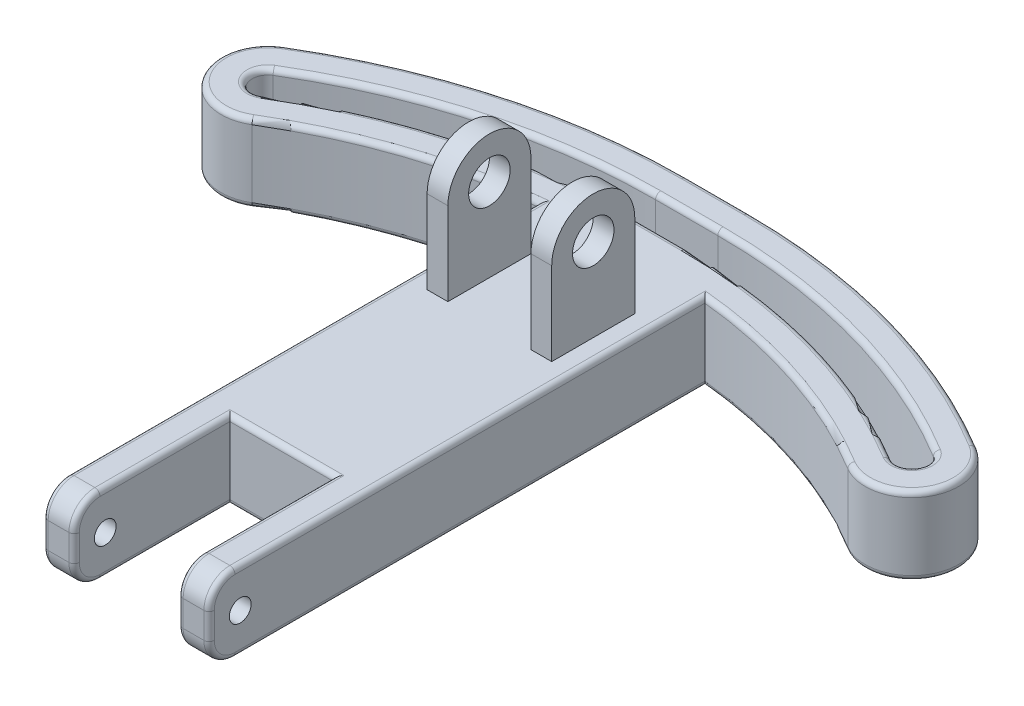
SolidWorks part; units mm, degrees
material "AISI 1020"
ref_plane "Front" through (0, 0, 0) normal (0, 0, 1) x (1, 0, 0)
ref_plane "Top" through (0, 0, 0) normal (0, 1, 0) x (1, 0, 0)
ref_plane "Right" through (0, 0, 0) normal (1, 0, 0) x (0, 0, -1)
sketch "Sketch1" plane through (0, 0, 0) normal (0, 1, 0) x (1, 0, 0)
  line L2 (70.9937, 406.4) -> (70.9937, 152.4)
  line L4 (70.9937, 482.6) -> (45.5937, 482.6)
  line L6 (20.1937, 406.4) -> (20.1937, 152.4)
  line L7 (70.9937, 457.2) -> (70.9937, 457.2)
  line L8 (70.9937, 406.4) -> (70.9937, 378.1596)
  line L9 (70.9937, 457.2) -> (70.9937, 378.1596) construction
  line L10 (70.9937, 457.2) -> (20.1937, 457.2)
  line L11 (70.9937, 431.8) -> (20.1937, 431.8)
  line L12 (20.1937, 482.6) -> (45.5937, 482.6)
  line L13 (57.6792, 127) -> (87.9271, 127)
  line L14 (87.9271, 127) -> (87.9271, 0)
  line L15 (87.9271, 0) -> (113.3271, 0)
  line L16 (113.3271, 0) -> (113.3271, 152.4)
  line L17 (113.3271, 152.4) -> (70.9937, 152.4)
  line L19 (20.1937, 152.4) -> (-22.1396, 152.4)
  line L20 (-22.1396, 152.4) -> (-22.1396, 0)
  line L21 (-22.1396, 0) -> (3.2604, 0)
  line L22 (3.2604, 0) -> (3.2604, 127)
  line L23 (3.2604, 127) -> (33.5083, 127)
  line L24 (90.9704, 127) -> (57.6792, 127)
  line L25 (86.1988, 127) -> (90.9704, 127)
  line L26 (33.5083, 127) -> (86.1988, 127)
  line L27 (45.5937, 482.6) -> (45.5937, 378.1596) construction
  arc A0 (70.9937, 406.4) -> (288.4438, 345.6809) centre (70.9937, -13.3308) cw
  arc A1 (70.9937, 482.6) -> (327.9208, 410.8577) centre (70.9937, -13.3308) cw
  arc A2 (327.9208, 410.8577) -> (288.4438, 345.6809) centre (308.1823, 378.2693) cw
  arc A3 (70.9937, 457.2) -> (314.7618, 389.1321) centre (70.9937, -13.3308) cw
  arc A4 (314.7618, 389.1321) -> (301.6028, 367.4065) centre (308.1823, 378.2693) cw
  arc A5 (70.9937, 431.8) -> (301.6028, 367.4065) centre (70.9937, -13.3308) cw
  arc A6 (20.1937, 406.4) -> (-197.2563, 345.6809) centre (20.1937, -13.3308) ccw
  arc A7 (20.1937, 431.8) -> (-210.4153, 367.4065) centre (20.1937, -13.3308) ccw
  arc A8 (20.1937, 457.2) -> (-223.5743, 389.1321) centre (20.1937, -13.3308) ccw
  arc A9 (-236.7333, 410.8577) -> (-197.2563, 345.6809) centre (-216.9948, 378.2693) ccw
  arc A10 (-223.5743, 389.1321) -> (-210.4153, 367.4065) centre (-216.9948, 378.2693) ccw
  arc A11 (20.1937, 482.6) -> (-236.7333, 410.8577) centre (20.1937, -13.3308) ccw
  point P28 (45.5937, 457.2)
  point P29 (45.5937, 431.8)
  dimension "D1" = 25.4
  dimension "D2" = 25.4
  dimension "D5" = 50.8
  dimension "D6" = 254
  dimension "D7" = 152.4
  dimension "D8" = 84.6667
  dimension "D9" = 25.4
  dimension "D3" = 76.2
  dimension "D4" = 25.4
extrude "Boss-Extrude1" add sketch "Sketch1" along normal blind 63.5 contours L16 L17 L2 L13 L14 L15 | L6 L26 L25 L24 L2 | L23 L26 L6 L19 L20 L21 L22 | L6 | L2 | A5 L9 A0 A2 A1 L4 L10 A3 A4 | L9 L11 | L12 A11 A9 A6 L11 A7 A10 A8 L10 region at (45.5937, 0, -326.3439)
ref_plane "Plane1" through (113.3271, 63.5, 0) normal (0, 0, -1) x (-1, 0, 0)
sketch "Sketch3" plane through (113.3271, 0, 0) normal (1, 0, 0) x (0, 0, -1)
  line L2 (0, 63.5) -> (0, 0) construction
  circle A0 centre (25.4, 31.75) radius 8.89
  point P5 (0, 31.75)
  dimension "D1" = 17.78
  dimension "D2" = 25.4
extrude "Cut-Extrude1" cut sketch "Sketch3" against normal through all
scale "Scale2" scale about centroid uniform scaling yes scale factor 3
sketch "Sketch4" plane through (121.7937, 0, 0) normal (1, 0, 0) x (0, 0, -1)
  line L1 (234.1211, 127) -> (437.3211, 127)
  line L2 (234.1211, 127) -> (234.1211, 330.2)
  line L4 (437.3211, 127) -> (437.3211, 330.2)
  line L7 (564.3211, 127) -> (-197.6789, 127) construction
  arc A0 (234.1211, 330.2) -> (437.3211, 330.2) centre (335.7211, 330.2) cw
  dimension "D1" = 203.2
  dimension "D2" = 203.2
  dimension "D3" = 127
extrude "Boss-Extrude2" add sketch "Sketch4" along normal blind 50.8 from offset 25.4
sketch "Sketch5" plane through (-30.6063, 0, 0) normal (-1, 0, 0) x (0, 0, 1)
  line L0 (-564.3211, 127) -> (197.6789, 127) construction
  line L1 (-437.3211, 127) -> (-234.1211, 127)
  line L2 (-437.3211, 127) -> (-437.3211, 330.2)
  line L4 (-234.1211, 127) -> (-234.1211, 330.2)
  arc A0 (-437.3211, 330.2) -> (-234.1211, 330.2) centre (-335.7211, 330.2) cw
  dimension "D3" = 101.6
  dimension "D1" = 203.2
  dimension "D2" = 127
extrude "Boss-Extrude3" add sketch "Sketch5" along normal blind 50.8 from offset 25.4 contours L4 A0 L2 L1
sketch "Sketch6" plane through (197.9937, 0, 0) normal (1, 0, 0) x (0, 0, -1)
  circle A0 centre (335.7211, 330.2) radius 50.8
  dimension "D1" = 101.6
fillet "Fillet1" radius 63.5 4 edges at (210.6937, -63.5, 654.8789) (-119.5063, -63.5, 654.8789) (-119.5063, 127, 654.8789) (210.6937, 127, 654.8789)
sketch "Sketch7" plane through (0, 0, 197.6789) normal (0, 0, -1) x (-1, 0, 0)
  line L0 (30.6063, 127) -> (157.6063, 127) construction
  line L1 (-248.7937, 127) -> (-121.7937, 127)
  line L2 (-248.7937, 127) -> (-248.7937, -63.5)
  line L3 (-248.7937, -63.5) -> (-121.7937, -63.5)
  line L4 (-121.7937, 127) -> (-121.7937, -63.5)
  line L5 (157.6063, 127) -> (30.6063, 127)
  line L6 (157.6063, 127) -> (157.6063, -63.5)
  line L7 (157.6063, -63.5) -> (30.6063, -63.5)
  line L8 (30.6063, 127) -> (30.6063, -63.5)
  line L9 (157.6063, 127) -> (157.6063, -63.5) construction
extrude "Boss-Extrude4" add sketch "Sketch7" along normal up to surface (755.5791 mm away) contours L5 L8 L7 L6 up to face at (-363.02, 31.75, -495.5848)
extrude "Boss-Extrude5" add sketch "Sketch7<3>" along normal up to surface (762 mm away) up to face at (454.2075, 31.75, -495.5848)
sketch "Sketch7<3>" plane through (0, 0, 197.6789) normal (0, 0, -1) x (-1, 0, 0) same geometry as "Sketch7"
extrude "Cut-Extrude2" cut sketch "Sketch6" against normal up to surface (304.8 mm away) contours A0 up to face at (-106.8063, 254, -335.7211)
fillet "Fillet2" radius 12.7 36 edges at (248.7937, -63.5, 16.7393) (248.7937, -44.9013, 636.2802) (248.7937, 31.75, 654.8789) (248.7937, 108.4013, 636.2802) (172.5937, -63.5, 432.6289) (172.5937, -44.9013, 636.2802) (172.5937, 31.75, 654.8789) (172.5937, 108.4013, 636.2802) (-81.4063, -63.5, 432.6289) (-81.4063, -44.9013, 636.2802) (-81.4063, 31.75, 654.8789) (-81.4063, 108.4013, 636.2802) (-157.6063, -63.5, 16.7393) (-157.6063, -44.9013, 636.2802) (-157.6063, 31.75, 654.8789) (-157.6063, 108.4013, 636.2802) (-389.7523, 127, -591.3196) (45.5937, 127, -640.5211) (480.9398, 127, -591.3196) (865.9477, 127, -460.1905) (501.4333, 127, -664.7121) (45.5937, 127, -716.7211) (-410.2458, 127, -664.7121) (-774.7602, 127, -460.1905) (-839.937, 127, -420.7136) (-430.7394, 127, -738.1045) (45.5937, 127, -792.9211) (521.9269, 127, -738.1045) (931.1245, 127, -420.7136) (521.2527, 127, -499.2803) (248.7937, 127, 16.7393) (172.5937, 127, 432.6289) (45.5937, 127, 273.8789) (-81.4063, 127, 432.6289) (-157.6063, 127, 16.7393) (-430.0653, 127, -499.2803)
fillet "Fillet3" radius 12.7 16 edges at (-410.2458, -63.5, -664.7121) (45.5937, -63.5, -716.7211) (501.4333, -63.5, -664.7121) (865.9477, -63.5, -460.1905) (480.9398, -63.5, -591.3196) (45.5937, -63.5, -640.5211) (-389.7523, -63.5, -591.3196) (-774.7602, -63.5, -460.1905) (931.1245, -63.5, -420.7136) (521.9269, -63.5, -738.1045) (45.5937, -63.5, -792.9211) (-430.7394, -63.5, -738.1045) (-839.937, -63.5, -420.7136) (-424.0103, -63.5, -501.2887) (45.5937, -63.5, 273.8789) (515.1978, -63.5, -501.2887)
